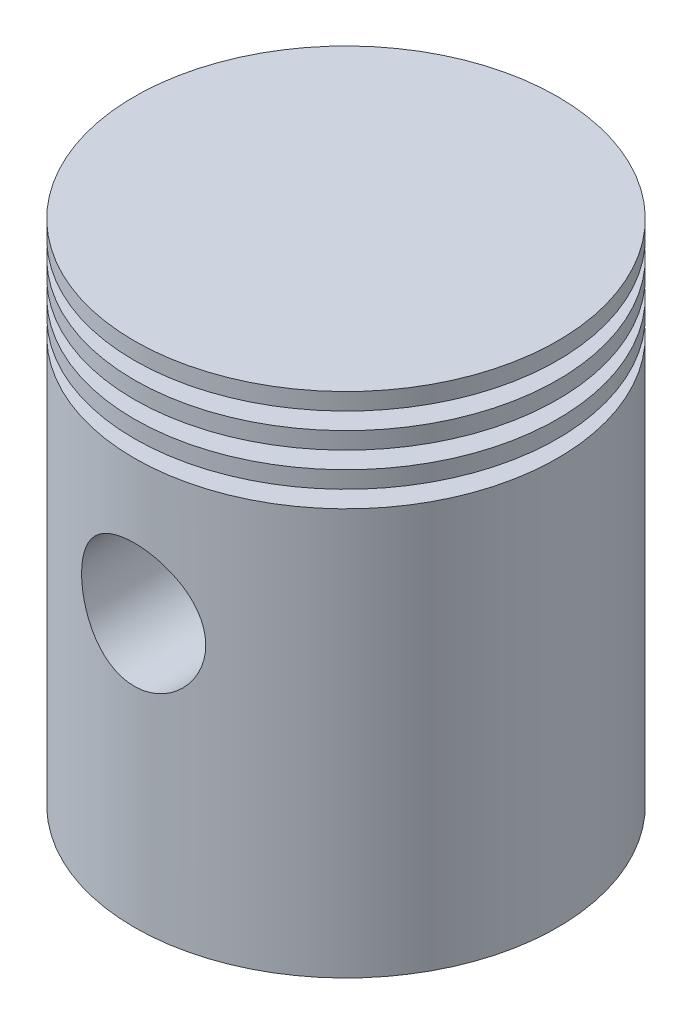
SolidWorks part; units mm, degrees
ref_plane "Front Plane" through (0, 0, 0) normal (0, 0, 1) x (1, 0, 0)
ref_plane "Top Plane" through (0, 0, 0) normal (0, 1, 0) x (1, 0, 0)
ref_plane "Right Plane" through (0, 0, 0) normal (1, 0, 0) x (0, 0, -1)
sketch "Sketch1" plane through (0, 0, 0) normal (0, 0, 1) x (1, 0, 0)
  line L0 (32.5, 0) -> (37.5, 0)
  line L1 (37.5, 0) -> (37.5, 72)
  line L2 (37.5, 72) -> (32.5, 72)
  line L3 (32.5, 72) -> (32.5, 75)
  line L4 (32.5, 75) -> (37.5, 75)
  line L5 (37.5, 75) -> (37.5, 78)
  line L6 (37.5, 78) -> (32.5, 78)
  line L7 (32.5, 78) -> (32.5, 81)
  line L8 (32.5, 81) -> (37.5, 81)
  line L9 (37.5, 81) -> (37.5, 84)
  line L10 (37.5, 84) -> (32.5, 84)
  line L11 (32.5, 84) -> (32.5, 87)
  line L12 (32.5, 87) -> (37.5, 87)
  line L13 (37.5, 87) -> (37.5, 90)
  line L14 (37.5, 90) -> (0, 90)
  line L15 (0, 0) -> (0, 25.1543) construction
  line L16 (32.5, 0) -> (32.5, 48)
  line L17 (32.5, 48) -> (27.5, 48)
  line L18 (27.5, 48) -> (27.5, 75)
  line L19 (0, 85) -> (17.5, 85)
  line L20 (0, 90) -> (0, 85)
  arc A0 (17.5, 85) -> (27.5, 75) centre (17.5, 75) cw
  point P24 (0, 0)
  point P26 (41.354, 48)
  dimension "D13" = 10
  dimension "D1" = 3
  dimension "D2" = 3
  dimension "D3" = 3
  dimension "D4" = 3
  dimension "D5" = 3
  dimension "D6" = 3
  dimension "D7" = 5
  dimension "D8" = 5
  dimension "D9" = 5
  dimension "D10" = 5
  dimension "D11" = 10
  dimension "D12" = 5
  dimension "D14" = 42
  dimension "D15" = 90
  dimension "D16" = 37.5
revolve "Revolve1" add sketch "Sketch1" angle 360 about L15
sketch "Sketch2" plane through (0, 0, 0) normal (0, 0, 1) x (1, 0, 0)
  line L0 (37.5, 90) -> (-37.5, 90) construction
  circle A0 centre (0, 48) radius 15
  point P4 (0, 0)
  dimension "D1" = 30
  dimension "D2" = 42
extrude "Boss-Extrude4" add sketch "Sketch2" against normal up to surface (21.3693 mm away) from offset 13 up to face at (0, 72, -37.5) offset against normal yes
extrude "Boss-Extrude5" add sketch "Sketch2<3>" along normal up to surface (21.3693 mm away) from offset 13 up to face at (0, 72, -37.5)
sketch "Sketch2<3>" plane through (0, 0, 0) normal (0, 0, 1) x (1, 0, 0) same geometry as "Sketch2"
sketch "Sketch4" plane through (0, 0, 0) normal (0, 0, 1) x (1, 0, 0)
  line L0 (37.5, 90) -> (-37.5, 90) construction
  circle A0 centre (0, 48) radius 11
  point P2 (0, 0)
  dimension "D1" = 22
  dimension "D2" = 42
extrude "Cut-Extrude2" cut sketch "Sketch4" against normal blind 50 and the other way blind 50
